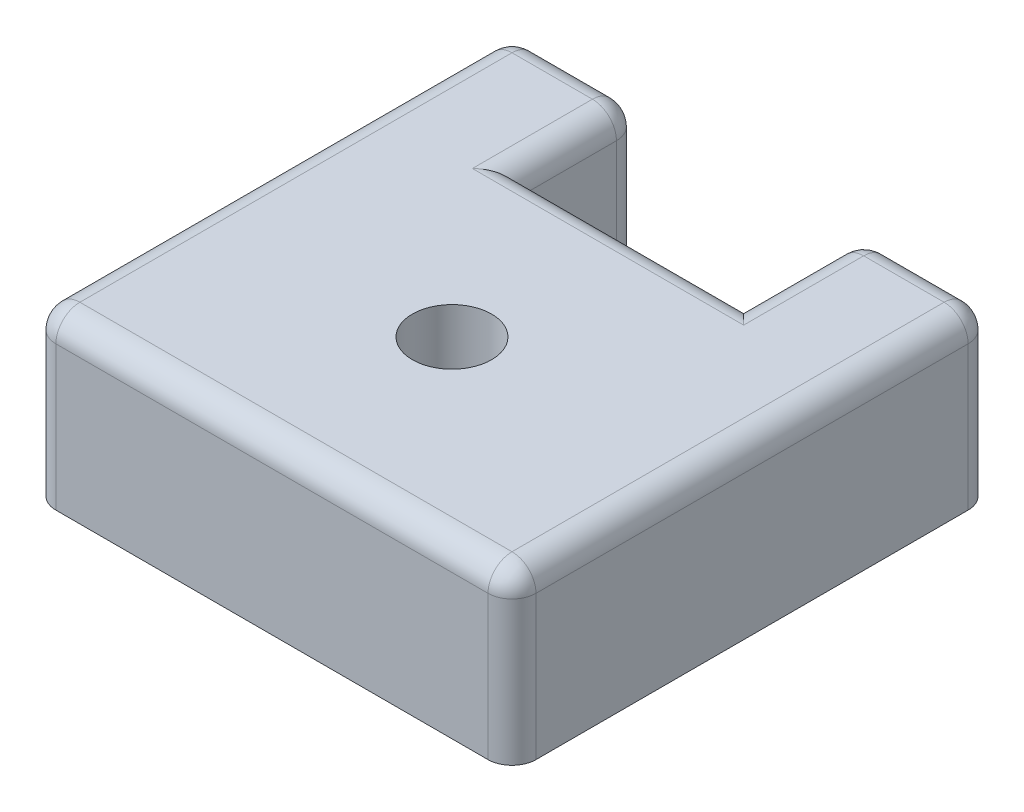
SolidWorks part; units mm, degrees
ref_plane "Front Plane" through (0, 0, 0) normal (0, 0, 1) x (1, 0, 0)
ref_plane "Top Plane" through (0, 0, 0) normal (0, 1, 0) x (1, 0, 0)
ref_plane "Right Plane" through (0, 0, 0) normal (1, 0, 0) x (0, 0, -1)
sketch "Sketch2" plane through (0, 0, 0) normal (0, 1, 0) x (1, 0, 0)
  line L0 (14.65, 20) -> (20, 20)
  line L1 (0, 0) -> (20, 0)
  line L2 (0, 0) -> (0, 20)
  line L3 (0, 20) -> (5.35, 20)
  line L4 (20, 0) -> (20, 20)
  line L6 (5.35, 20) -> (5.35, 15)
  line L7 (5.35, 15) -> (14.65, 15)
  line L8 (14.65, 20) -> (14.65, 15)
  dimension "D1" = 20
  dimension "D2" = 9.3
  dimension "D3" = 20
  dimension "D4" = 5
  dimension "D5" = 5.35
extrude "Boss-Extrude1" add sketch "Sketch2" along normal blind 7 contours L4 L0 L8 L7 L6 L3 L2 L1
fillet "Fillet1" radius 1 14 edges at (0, 7, -10) (2.675, 7, -20) (5.35, 7, -17.5) (10, 7, -15) (14.65, 7, -17.5) (17.325, 7, -20) (20, 7, -10) (10, 7, 0) (0, 3.5, 0) (20, 3.5, 0) (20, 3.5, -20) (0, 3.5, -20) (14.65, 3.5, -20) (5.35, 3.5, -20)
sketch "Sketch3" plane through (0, 7, 0) normal (0, 1, 0) x (1, 0, 0)
  line L0 (10, 1) -> (10, 14) construction
  line L1 (1, 1) -> (19, 1) construction
  line L2 (15.65, 14) -> (4.35, 14) construction
  circle A0 centre (10, 7.5) radius 1.65
  dimension "D1" = 3.3
extrude "Cut-Extrude1" cut sketch "Sketch3" against normal through all
